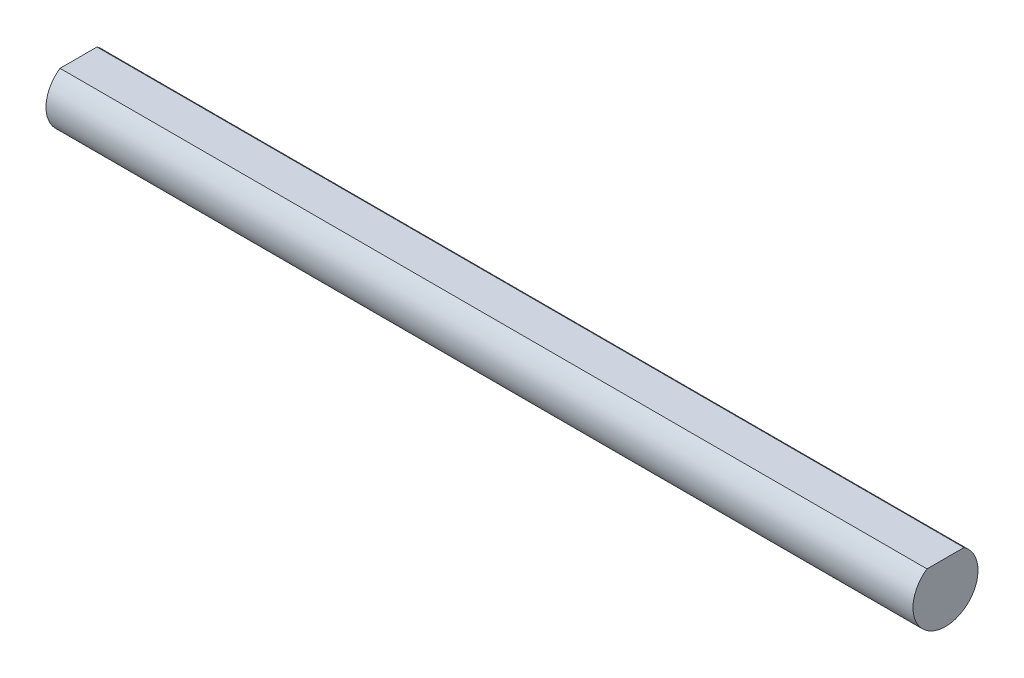
SolidWorks part; units mm, degrees
ref_plane "Front Plane" through (0, 0, 0) normal (0, 0, 1) x (1, 0, 0)
ref_plane "Top Plane" through (0, 0, 0) normal (0, 1, 0) x (1, 0, 0)
ref_plane "Right Plane" through (0, 0, 0) normal (1, 0, 0) x (0, 0, -1)
sketch "Sketch1" plane through (0, 0, 0) normal (1, 0, 0) x (0, 0, -1)
  line L1 (1.0667, 1.542) -> (-1.0667, 1.542)
  arc A0 (-1.0667, 1.542) -> (1.0667, 1.542) centre (0, 0) ccw
  dimension "D1" = 3.75
extrude "Boss-Extrude1" add sketch "Sketch1" along normal mid plane 50
